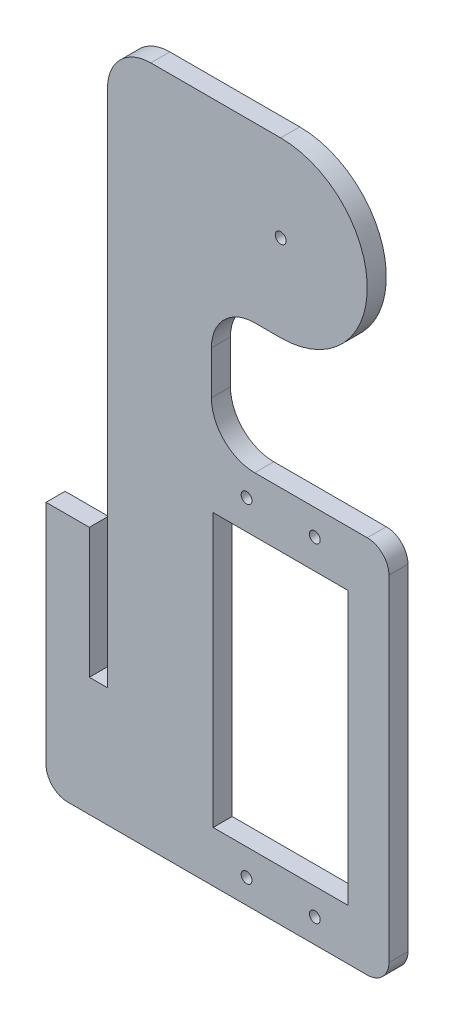
SolidWorks part; units mm, degrees
ref_plane "Front Plane" through (0, 0, 0) normal (0, 0, 1) x (1, 0, 0)
ref_plane "Top Plane" through (0, 0, 0) normal (0, 1, 0) x (1, 0, 0)
ref_plane "Right Plane" through (0, 0, 0) normal (1, 0, 0) x (0, 0, -1)
sketch "Sketch1" plane through (0, 0, 0) normal (0, 0, 1) x (1, 0, 0)
  line L1 (6.4409, 4.7342) -> (50.8, 4.7342)
  line L2 (0.508, 9.525) -> (0.508, 41.2272)
  line L3 (0.508, 41.2272) -> (6.858, 41.2272)
  line L4 (50.8, 4.7342) -> (50.8, 36.3432)
  line L5 (25.019, 52.1772) -> (44.831, 52.1772)
  line L6 (6.858, 41.2272) -> (6.858, 22.1772)
  line L7 (6.858, 22.1772) -> (9.525, 22.1772)
  line L8 (9.525, 38.1) -> (9.525, 22.1772)
  line L9 (25.019, 52.1772) -> (25.019, 12.1772)
  line L10 (9.525, 38.1) -> (9.525, 104.7272)
  line L11 (9.525, 104.7272) -> (34.925, 104.7272)
  line L12 (50.8, 36.3432) -> (50.8, 60.2848)
  line L13 (25.019, 12.1772) -> (44.831, 12.1772)
  line L14 (44.831, 52.1772) -> (44.831, 12.1772)
  line L15 (25.019, 52.1772) -> (44.831, 12.1772) construction
  line L16 (25.019, 12.1772) -> (44.831, 52.1772) construction
  line L17 (50.8, 60.2848) -> (24.765, 60.2848)
  line L21 (34.925, 79.3272) -> (24.765, 79.3272)
  line L22 (24.765, 60.2848) -> (24.765, 79.3272)
  line L25 (6.4409, 4.7342) -> (0.508, 4.7342)
  line L26 (0.508, 9.525) -> (0.508, 4.7342)
  circle A0 centre (34.925, 92.0272) radius 0.7937
  arc A1 (34.925, 79.3272) -> (34.925, 104.7272) centre (34.925, 92.0272) ccw
  circle A2 centre (29.9212, 8.2834) radius 0.7937
  circle A3 centre (39.9288, 8.2834) radius 0.7937
  circle A4 centre (29.9212, 56.518) radius 0.7937
  circle A5 centre (39.9288, 56.518) radius 0.7937
  point P11 (34.925, 32.1772)
  dimension "D17" = 12.7
  dimension "D10" = 13.8938
  dimension "D11" = 4.9022
  dimension "D15" = 34.3408
  dimension "D2" = 82.55
  dimension "D3" = 6.35
  dimension "D4" = 2.667
  dimension "D5" = 19.05
  dimension "D6" = 25.4
  dimension "D7" = 40
  dimension "D8" = 19.812
  dimension "D9" = 10
  dimension "D12" = 15.24
  dimension "D13" = 25.4
  dimension "D14" = 4.9022
  dimension "D18" = 25.4
extrude "Boss-Extrude1" add sketch "Sketch1" along normal blind 2.794
fillet "Fillet1" radius 6.35 2 edges at (24.765, 60.2848, 1.397) (24.765, 79.3272, 1.397)
fillet "Fillet2" radius 6.35 1 edges at (9.525, 104.7272, 1.397)
fillet "Fillet3" radius 3.175 3 edges at (0.508, 4.7342, 1.397) (50.8, 4.7342, 1.397) (50.8, 60.2848, 1.397)
